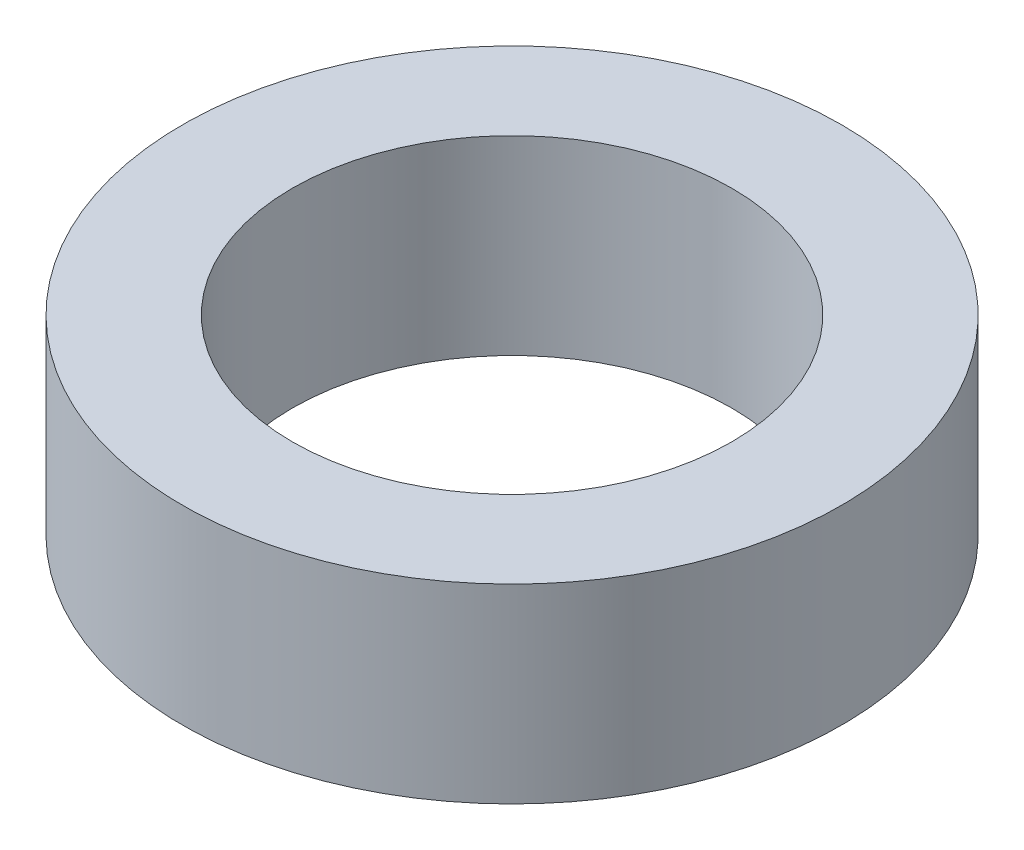
SolidWorks part; units mm, degrees
ref_plane "Front Plane" through (0, 0, 0) normal (0, 0, 1) x (1, 0, 0)
ref_plane "Top Plane" through (0, 0, 0) normal (0, 1, 0) x (1, 0, 0)
ref_plane "Right Plane" through (0, 0, 0) normal (1, 0, 0) x (0, 0, -1)
sketch "Sketch1" plane through (0, 0, 0) normal (0, 1, 0) x (1, 0, 0)
  circle A0 centre (0, 0) radius 22.5
  dimension "FLANGE_OD" = 45
extrude "Boss-Extrude1" add sketch "Sketch1" along normal blind 13
sketch "Sketch2" plane through (0, 0, 0) normal (0, 1, 0) x (1, 0, 0)
  circle A0 centre (0, 0) radius 15
  dimension "BORE_D" = 30
extrude "Cut-Extrude1" cut sketch "Sketch2" along normal through all
sketch "Sketch3" plane through (0, 13, 0) normal (0, 1, 0) x (1, 0, 0)
  circle A0 centre (0, 0) radius 9.0354 construction
  circle A1 centre (-9.0354, 0) radius 1.5
  dimension "BOLT_D" = 3
  dimension "BOLT_PCD" = 18.0708
extrude "Cut-Extrude2" cut sketch "Sketch3" against normal blind 10.0922 rebuild error yes
pattern_circular "CirPattern1" count 3 over 360 rebuild error yes
